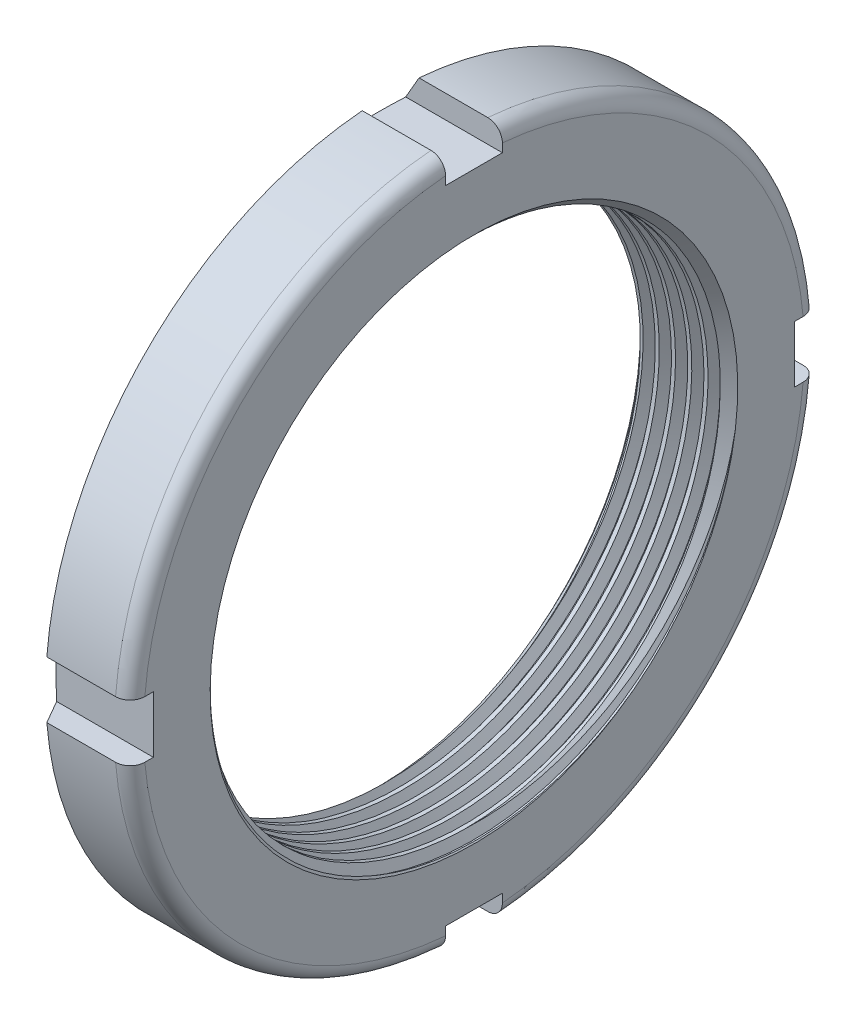
SolidWorks part; units mm, degrees
ref_plane "Front Plane" through (0, 0, 0) normal (0, 0, 1) x (1, 0, 0)
ref_plane "Top Plane" through (0, 0, 0) normal (0, 1, 0) x (1, 0, 0)
ref_plane "Right Plane" through (0, 0, 0) normal (1, 0, 0) x (0, 0, -1)
ref_plane "Plane1" through (0, 0, 0) normal (0, 0, -1) x (-1, 0, 0)
sketch "Sketch1" plane through (0, 0, 0) normal (0, 0, -1) x (-1, 0, 0)
  line L0 (-12, 42.5) -> (-12, 0)
  line L1 (-12, 0) -> (0, 0)
  line L2 (0, 0) -> (0, 42.5)
  line L3 (0, 42.5) -> (-12, 42.5)
  line L4 (-12, 0) -> (0, 0) construction
revolve "Revolve1" add sketch "Sketch1" angle 360 about L4 reverse direction yes
sketch "Sketch2" plane through (12, 0, 0) normal (1, 0, 0) x (0, 0, -1)
  line L0 (42.3556, 3.5) -> (39.5, 3.5)
  line L1 (39.5, 3.5) -> (39.5, -3.5)
  line L2 (39.5, -3.5) -> (42.3556, -3.5)
  arc A0 (42.3556, -3.5) -> (42.3556, 3.5) centre (0, 0) ccw
extrude "Cut-Extrude1" cut sketch "Sketch2" against normal through all
sketch "Sketch3" plane through (12, 0, 0) normal (1, 0, 0) x (0, 0, -1)
  line L0 (3.5, -42.3556) -> (3.5, -39.5)
  line L1 (3.5, -39.5) -> (-3.5, -39.5)
  line L2 (-3.5, -39.5) -> (-3.5, -42.3556)
  arc A0 (-3.5, -42.3556) -> (3.5, -42.3556) centre (0, 0) ccw
extrude "Cut-Extrude2" cut sketch "Sketch3" against normal through all
sketch "Sketch4" plane through (12, 0, 0) normal (1, 0, 0) x (0, 0, -1)
  line L0 (-42.3556, -3.5) -> (-39.5, -3.5)
  line L1 (-39.5, -3.5) -> (-39.5, 3.5)
  line L2 (-39.5, 3.5) -> (-42.3556, 3.5)
  arc A0 (-42.3556, 3.5) -> (-42.3556, -3.5) centre (0, 0) ccw
extrude "Cut-Extrude3" cut sketch "Sketch4" against normal through all
sketch "Sketch5" plane through (12, 0, 0) normal (1, 0, 0) x (0, 0, -1)
  line L0 (-3.5, 42.3556) -> (-3.5, 39.5)
  line L1 (-3.5, 39.5) -> (3.5, 39.5)
  line L2 (3.5, 39.5) -> (3.5, 42.3556)
  arc A0 (3.5, 42.3556) -> (-3.5, 42.3556) centre (0, 0) ccw
extrude "Cut-Extrude4" cut sketch "Sketch5" against normal through all
hole_wizard "M56 Clearance Hole1" positions "Sketch7" profile "Sketch6" hole size "M56" standard "ANSI Metric"
sketch "Sketch7" plane through (0, 0, 0) normal (-1, 0, 0) x (0, 0, 1)
  point P0 (0, 0)
sketch "Sketch6" plane through (0, 0, 0) normal (0, 1, 0) x (0, 0, 1)
  line L0 (0, 0) -> (0, 12)
  line L1 (0, 12) -> (31.4175, 12)
  line L2 (31.4175, 12) -> (31.4175, 0)
  line L5 (31.4175, 0) -> (0, 0)
  line L11 (0, -6.35) -> (0, 107.95) construction
  dimension "Thru Hole Dia." = 62.835
  dimension "Thru Hole Depth" = 12
chamfer "Chamfer1" distance 3 angle 30 4 edges at (0, 30.052, 30.052) (0, -30.052, -30.052) (0, -30.052, 30.052) (0, 30.052, -30.052) first distance on face at (0, 0, 31.4175)
chamfer "Chamfer2" distance 1.0825 angle 45 2 edges at (12, 0, 31.4175) (0, 0, 31.4175)
fillet "Fillet1" radius 1.8 4 edges at (12, 30.052, -30.052) (12, -30.052, -30.052) (12, 30.052, 30.052) (12, -30.052, 30.052) tangent propagation no
thread "Thread1" pitch 2 method cut profile "Thread Profile2" start angle 0, offset 3, length 15, pitch 2, diameter 62.835
ref_plane "Plane3" through (13.9175, 0, 31.4175) normal (0, -1, 0) x (0, 0, 1)
sketch "Thread Profile2" plane through (13.9175, 0, 31.4175) normal (0, -1, 0) x (0, 0, 1)
  line L0 (0, 0) -> (0, 2) construction
  line L1 (0, 0) -> (1.0825, 0.625)
  line L2 (1.0825, 0.625) -> (1.0825, 0.875)
  line L3 (1.0825, 0.875) -> (0, 1.5)
  line L4 (1.0825, 0.75) -> (0, 0.75) construction
  line L11 (0, 0) -> (0, 1.5)
  point P2 (0, 0)
  dimension "Pitch" = 2
  dimension "Profile_Angle" = 60
  dimension "Profile_Land" = 0.25
  dimension "Profile_Height" = 1.0825
